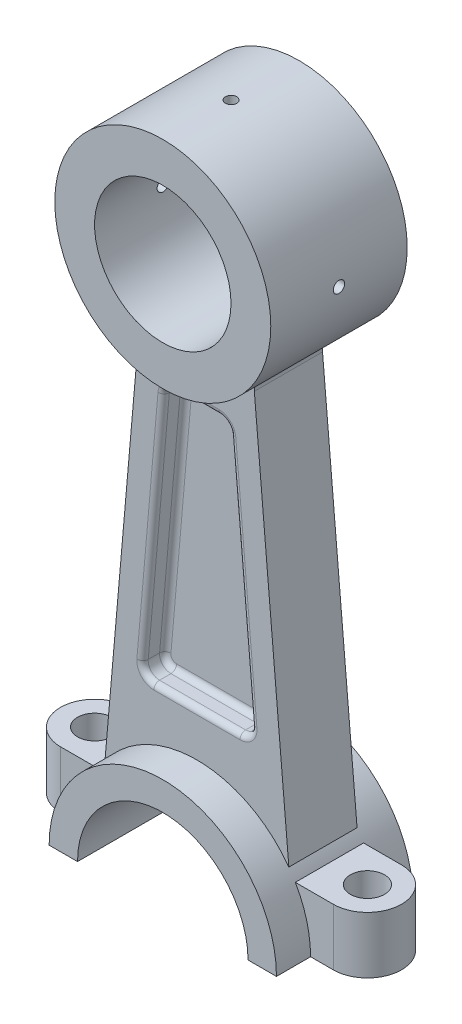
SolidWorks part; units mm, degrees
note: The reader was unsure of these and kept them because the rebuilt part matched: shared geometry of "Çizim1<3>", "Çizim1<4>", "Çizim1<5>".
material "Gri Dökme Demir"
ref_plane "Ön Düzlem" through (0, 0, 0) normal (0, 0, 1) x (1, 0, 0)
ref_plane "Üst Düzlem" through (0, 0, 0) normal (0, 1, 0) x (1, 0, 0)
ref_plane "Sağ Düzlem" through (0, 0, 0) normal (1, 0, 0) x (0, 0, -1)
sketch "Çizim1" plane through (0, 0, 0) normal (0, 0, 1) x (1, 0, 0)
  line L0 (20, 0) -> (-20, 0) construction
  line L1 (-20, 0) -> (-15, 0)
  line L2 (15, 0) -> (20, 0)
  line L3 (-17.3205, 10) -> (-30, 10)
  line L4 (0, 0) -> (0, 20) construction
  line L5 (-30, 10) -> (-30, 0)
  line L6 (-30, 0) -> (-20, 0)
  line L7 (-24, 10) -> (-24, 0)
  line L8 (30, 0) -> (20, 0)
  line L9 (24, 10) -> (24, 0)
  line L10 (17.3205, 10) -> (30, 10)
  line L11 (30, 10) -> (30, 0)
  line L12 (-16.1801, 11.7561) -> (-10, 82.3945)
  line L13 (16.1801, 11.7561) -> (10, 82.3945)
  line L14 (0, 20) -> (0, 98.55) construction
  arc A0 (15, 0) -> (-15, 0) centre (0, 0) ccw
  arc A1 (20, 0) -> (-20, 0) centre (0, 0) ccw
  circle A2 centre (0, 98.55) radius 19
  circle A3 centre (0, 98.55) radius 12
  point P7 (0, 0)
  point P23 (-11.8492, 83.6975)
  point P25 (11.8492, 83.6975)
  point P26 (-11.8492, 15.8997)
  point P27 (-15, 13.1399)
  point P29 (-8.5725, 81.5938)
  point P30 (-4.5082, 80.0926)
  point P31 (0, 0)
  dimension "D1" = 30
  dimension "D2" = 40
  dimension "D7" = 24
  dimension "D8" = 38
  dimension "D3" = 10
  dimension "D4" = 30
  dimension "D5" = 6
  dimension "D6" = 98.55
  dimension "D9" = 5
  dimension "D10" = 10
extrude "Yükseklik-Ekstrüzyon1" add sketch "Çizim1" along normal mid plane 24 contours L2 A1 L1 A0 | A3 | A2
extrude "Yükseklik-Ekstrüzyon2" add sketch "Çizim1<3>" along normal mid plane 12 contours A2 L12 A1 L13
sketch "Çizim1<3>" plane through (0, 0, 0) normal (0, 0, 1) x (1, 0, 0) same geometry as "Çizim1"
extrude "Yükseklik-Ekstrüzyon3" add sketch "Çizim1<4>" along normal mid plane 24 contours A2 A3
sketch "Çizim1<4>" plane through (0, 0, 0) normal (0, 0, 1) x (1, 0, 0) same geometry as "Çizim1"
extrude "Yükseklik-Ekstrüzyon4" add sketch "Çizim1<5>" along normal mid plane 12 contours L7 L3 L5 L6 | A1 L3 L7 L6 | A1 L8 L9 L10 | L11 L10 L9 L8
sketch "Çizim1<5>" plane through (0, 0, 0) normal (0, 0, 1) x (1, 0, 0) same geometry as "Çizim1"
sketch "Çizim2" plane through (0, 10, 0) normal (0, 1, 0) x (1, 0, 0)
  line L0 (-30, 0) -> (-24, 0) construction
  line L1 (-30, -6) -> (-30, 6) construction
  line L2 (-17.3205, -6) -> (-30, -6) construction
  line L3 (-24, 6) -> (-24, -6)
  line L4 (-24, 6) -> (-30, 6)
  line L5 (-30, 6) -> (-30, -6)
  line L6 (-30, -6) -> (-24, -6)
  arc A0 (-24, -6) -> (-24, 6) centre (-24, 0) cw
  line M4 (-17.3205, 6) -> (-30, 6)
  line M5 (-30, 6) -> (-30, -6)
  line M6 (-30, -6) -> (-17.3205, -6)
  dimension "D2" = 6
  dimension "D1" = 6
extrude "Kes-Ekstrüzyon1" cut sketch "Çizim2" against normal through all contours A0 M5 M4 | A0 L5 M6
sketch "Çizim3" plane through (0, 10, 0) normal (0, 1, 0) x (1, 0, 0)
  line L0 (-24, 0) -> (-24, 6) construction
hole_wizard "Ø6.0 (6) Çap Delik1" positions "Çizim6" profile "Çizim7" hole size "Ø6.0" standard "ISO" end condition through all
sketch "Çizim6" plane through (0, 10, 0) normal (0, 1, 0) x (1, 0, 0)
  point P0 (-24, 0)
sketch "Çizim7" plane through (-24, 10, 0) normal (1, 0, 0) x (0, 0, 1)
  line L0 (0, 0) -> (0, 10)
  line L1 (0, 10) -> (3, 10)
  line L2 (3, 10) -> (3, 0)
  line L5 (3, 0) -> (0, 0)
  line L11 (0, -6.35) -> (0, 107.95) construction
  dimension "Thru Hole Dia." = 6
  dimension "Thru Hole Depth" = 10
mirror "Aynalama1" about plane through (0, 0, 0) normal (1, 0, 0) of "Ø6.0 (6) Çap Delik1"
sketch "Çizim8" plane through (0, 0, 6) normal (0, 0, 1) x (1, 0, 0)
  line L0 (0, 79.55) -> (0, 20) construction
  line L1 (5.8455, 72.5127) -> (9.5625, 30.0267)
  line L2 (16.1801, 11.7561) -> (10, 82.3945) construction
  line L3 (16.1801, 11.7561) -> (10, 82.3945) construction
  line L4 (3.8531, 74.3383) -> (-3.8531, 74.3383)
  line L5 (7.5701, 27.8524) -> (-7.5701, 27.8524)
  line L6 (-5.8455, 72.5127) -> (-9.5625, 30.0267)
  arc A0 (-10, 82.3945) -> (10, 82.3945) centre (0, 98.55) ccw construction
  arc A1 (20, 0) -> (-20, 0) centre (0, 0) ccw construction
  arc A2 (5.8455, 72.5127) -> (3.8531, 74.3383) centre (3.8531, 72.3383) ccw
  arc A3 (-5.8455, 72.5127) -> (-3.8531, 74.3383) centre (-3.8531, 72.3383) cw
  arc A4 (7.5701, 27.8524) -> (9.5625, 30.0267) centre (7.5701, 29.8524) ccw
  arc A5 (-9.5625, 30.0267) -> (-7.5701, 27.8524) centre (-7.5701, 29.8524) ccw
  point P14 (0, 27.8524)
  point P16 (0, 74.3383)
  point P18 (5.6857, 74.3383)
  point P21 (-5.6857, 74.3383)
  point P24 (9.7527, 27.8524)
  point P27 (-9.7527, 27.8524)
  dimension "D2" = 5.6857
  dimension "D3" = 9.7527
  dimension "D4" = 2
  dimension "D1" = 5
extrude "Kes-Ekstrüzyon2" cut sketch "Çizim8" against normal blind 4
mirror "Aynalama2" about plane through (0, 0, 0) normal (0, 0, 1) of "Kes-Ekstrüzyon2"
fillet "Radyus1" radius 1 16 edges at (-5.2042, 73.8129, 6) (0, 74.3383, 6) (5.2042, 73.8129, 6) (7.704, 51.2697, 6) (9.0447, 28.5012, 6) (0, 27.8524, 6) (-9.0447, 28.5012, 6) (-5.2042, 73.8129, 2) (0, 74.3383, 2) (5.2042, 73.8129, 2) (7.704, 51.2697, 2) (9.0447, 28.5012, 2) (0, 27.8524, 2) (-9.0447, 28.5012, 2) (-7.704, 51.2697, 6) (-7.704, 51.2697, 2)
fillet "Radyus2" radius 1 16 edges at (-5.2042, 73.8129, -6) (0, 74.3383, -6) (5.2042, 73.8129, -6) (7.704, 51.2697, -6) (9.0447, 28.5012, -6) (0, 27.8524, -6) (-9.0447, 28.5012, -6) (-5.2042, 73.8129, -2) (0, 74.3383, -2) (5.2042, 73.8129, -2) (7.704, 51.2697, -2) (9.0447, 28.5012, -2) (0, 27.8524, -2) (-9.0447, 28.5012, -2) (-7.704, 51.2697, -6) (-7.704, 51.2697, -2)
mirror "Aynalama3" about plane through (0, 0, 0) normal (1, 0, 0) of "Kes-Ekstrüzyon1"
ref_plane "Düzlem1" through (19, 0, 0) normal (1, 0, 0) x (0, 0, -1)
sketch "Çizim9" plane through (19, 0, 0) normal (1, 0, 0) x (0, 0, -1)
  line L0 (0, 117.55) -> (0, 98.55) construction
  line L1 (12, 117.55) -> (-12, 117.55) construction
  line L2 (12, 98.55) -> (0, 98.55) construction
  line L3 (12, 79.55) -> (12, 117.55) construction
  circle A0 centre (0, 98.55) radius 1
  dimension "D1" = 2
extrude "Kes-Ekstrüzyon3" cut sketch "Çizim9" against normal through all
ref_plane "Düzlem2" through (0, 117.55, 0) normal (0, 1, 0) x (1, 0, 0)
sketch "Çizim10" plane through (0, 117.55, 0) normal (0, 1, 0) x (1, 0, 0)
  line L0 (0, 12) -> (0, -5.5128) construction
  line L1 (12, 12) -> (-12, 12) construction
  circle A0 centre (0, 0) radius 1
  dimension "D1" = 2
extrude "Kes-Ekstrüzyon4" cut sketch "Çizim10" against normal blind 16
fillet "Radyus3" radius 2 2 edges at (-10, 82.3945, 0) (10, 82.3945, 0)
